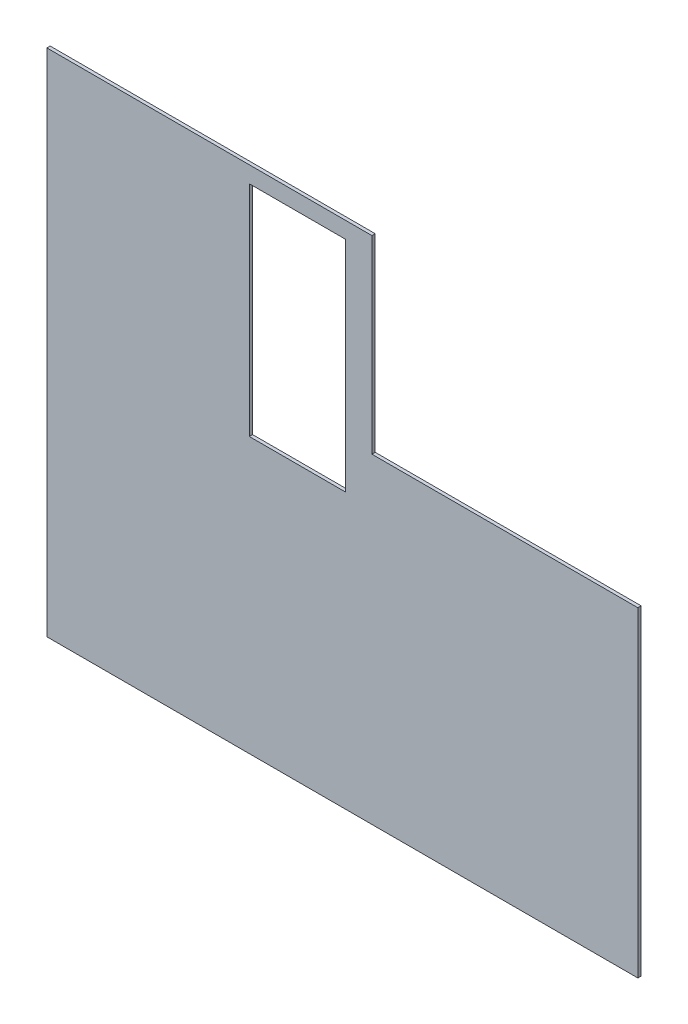
SolidWorks part; units mm, degrees
ref_plane "Plan de face" through (0, 0, 0) normal (0, 0, 1) x (1, 0, 0)
ref_plane "Plan de dessus" through (0, 0, 0) normal (0, 1, 0) x (1, 0, 0)
ref_plane "Plan de droite" through (0, 0, 0) normal (1, 0, 0) x (0, 0, -1)
sketch "Esquisse1" plane through (0, 0, 0) normal (0, 0, 1) x (1, 0, 0)
  line L0 (589.2231, -367.6438) -> (49.2231, -367.6438)
  line L1 (49.2231, 98.3562) -> (346.2231, 98.3562)
  line L2 (49.2231, 98.3562) -> (49.2231, -367.6438)
  line L4 (346.2231, 98.3562) -> (346.2231, -74.6438)
  line L5 (322.2231, -116.6438) -> (234.2231, -116.6438)
  line L6 (322.2231, -116.6438) -> (322.2231, 83.3562)
  line L7 (322.2231, 83.3562) -> (234.2231, 83.3562)
  line L8 (234.2231, -116.6438) -> (234.2231, 83.3562)
  line L11 (346.2231, -74.6438) -> (589.2231, -74.6438)
  line L12 (589.2231, -367.6438) -> (589.2231, -74.6438)
  dimension "D2" = 466
  dimension "D3" = 200
  dimension "D4" = 88
  dimension "D5" = 15
  dimension "D6" = 185
  dimension "D7" = 243
  dimension "D8" = 293
  dimension "D1" = 540
extrude "Boss.-Extru.1" add sketch "Esquisse1" along normal blind 3
equation "\"EpaisseurPlaque\"= 3"
equation "\"D1@Boss.-Extru.1\"=\"EpaisseurPlaque\""
equation "\"ProfondeurBoite\"=460"
equation "\"LongueurSyphon\"=170"
equation "\"LargeurSyphon\"=120"
equation "\"HauteurCoteDroit\"= 490"
equation "\"HauteurCoteGauche\"= 540"
equation "\"HauteurSolSyphon\"= 300"
equation "\"HauteurSyphon\"=\"HauteurCoteGauche\"-\"HauteurSolSyphon\""
equation "\"LargeurBoite\"= \"LargeurDroite\" + \"LargeurGauche\" + \"LargeurSyphon\""
equation "\"D2@Esquisse1\"=\"ProfondeurBoite\" + 2 * \"EpaisseurPlaque\""
equation "\"D1@Esquisse1\"=\"HauteurCoteGauche\""
equation "\"LargeurDroite\"=10"
equation "\"LargeurGauche\"=150"
equation "\"D7@Esquisse1\"=\"HauteurSyphon\" + \"EpaisseurPlaque\""
equation "\"D8@Esquisse1\"=\"ProfondeurBoite\" - \"LongueurSyphon\" + \"EpaisseurPlaque\""
